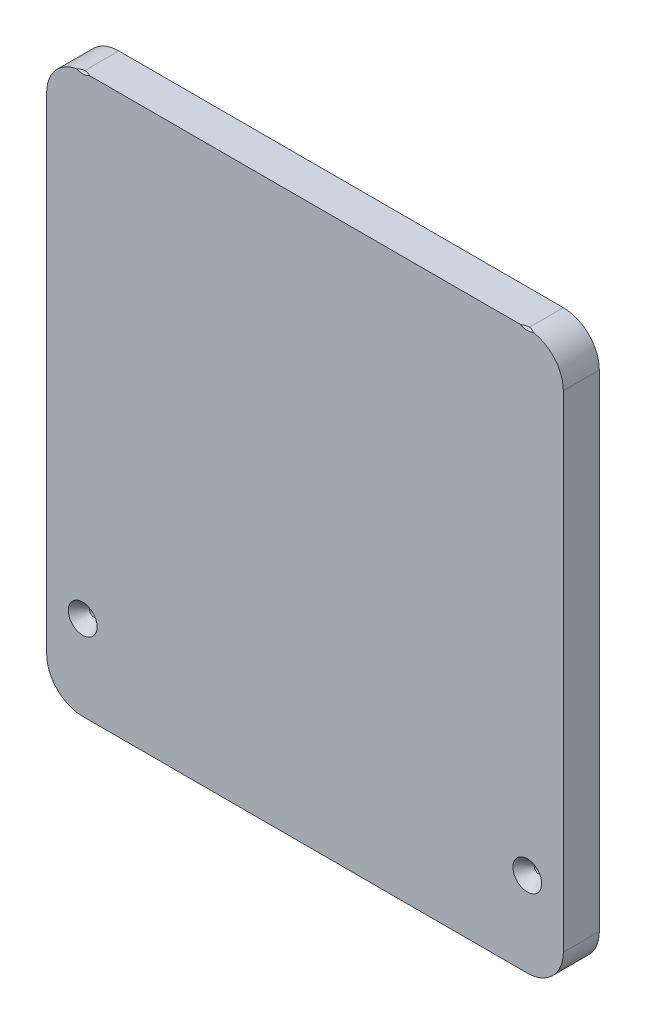
SolidWorks part; units mm, degrees
material "Beech"
ref_plane "Front Plane" through (0, 0, 0) normal (0, 0, 1) x (1, 0, 0)
ref_plane "Top Plane" through (0, 0, 0) normal (0, 1, 0) x (1, 0, 0)
ref_plane "Right Plane" through (0, 0, 0) normal (1, 0, 0) x (0, 0, -1)
sketch "Sketch1" plane through (0, 0, 0) normal (0, 0, 1) x (1, 0, 0)
  line L0 (139.05, 899.8522) -> (139.05, 151.949) construction
  line L1 (-43.1, 899.8522) -> (-43.1, 151.949) construction
  line L2 (-43.1, 906.2022) -> (139.05, 906.2022) construction
  line L8 (139.05, 668.0772) -> (139.05, 864.9272)
  line L9 (139.05, 864.9272) -> (-43.1, 864.9272)
  line L10 (-43.1, 864.9272) -> (-43.1, 668.0772)
  line L11 (-43.1, 668.0772) -> (139.05, 668.0772)
  dimension "D1" = 196.85
  dimension "D2" = 41.275
extrude "Boss-Extrude1" add sketch "Sketch1" along normal blind 12.7
fillet "Fillet1" radius 12.7 4 edges at (139.05, 864.9272, 6.35) (139.05, 668.0772, 6.35) (-43.1, 668.0772, 6.35) (-43.1, 864.9272, 6.35)
hole_wizard "Hole1" positions "Sketch2" profile "Sketch3" legacy
sketch "Sketch2" plane through (47.975, -440.812, 12.7) normal (0, 0, 1) x (1, 0, 0)
  point P0 (-78.375, 1310.1878)
  point P3 (-78.375, 1138.7378)
  point P6 (78.375, 1138.7378)
  point P9 (78.375, 1310.1878)
sketch "Sketch3" plane through (-30.4, 869.3757, 12.7) normal (1, 0, 0) x (0, -1, 0)
  line L0 (0, 0) -> (0, 32.7039)
  line L1 (0, 32.7039) -> (1.5875, 31.75)
  line L2 (1.5875, 31.75) -> (1.5875, 4.0177)
  line L3 (1.5875, 4.0177) -> (5.08, 0)
  line L4 (5.08, 0) -> (0, 0)
  line L5 (0, -14.3089) -> (0, 102.4216) construction
  line L6 (0, 32.7039) -> (-1.5875, 31.75) construction
  line L7 (-1.5875, 4.0177) -> (-5.08, 0) construction
  dimension "Diameter" = 3.175
  dimension "Depth" = 31.75
  dimension "C-Sink Diameter" = 10.16
  dimension "C-Sink Angle" = 82
  dimension "Drill Angle" = 118
